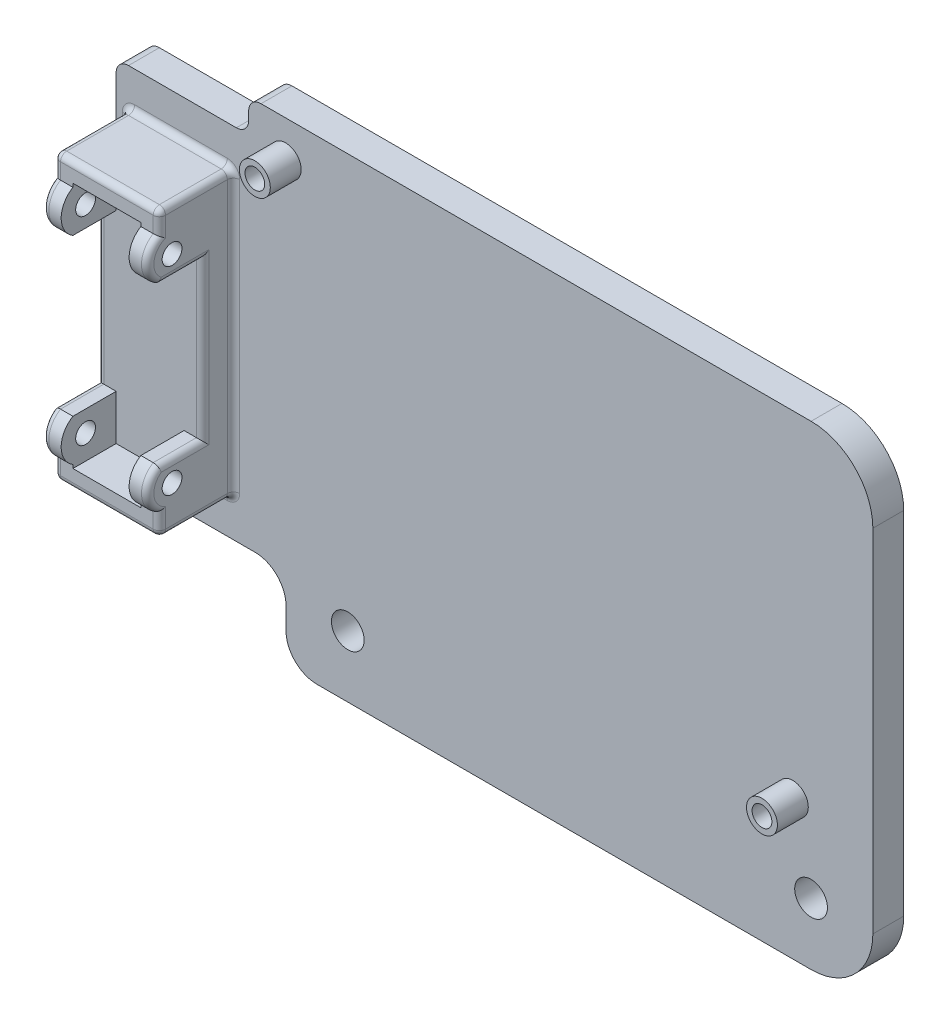
SolidWorks part; units mm, degrees
ref_plane "Front Plane" through (0, 0, 0) normal (0, 0, 1) x (1, 0, 0)
ref_plane "Top Plane" through (0, 0, 0) normal (0, 1, 0) x (1, 0, 0)
ref_plane "Right Plane" through (0, 0, 0) normal (1, 0, 0) x (0, 0, -1)
sketch "Sketch1" plane through (0, 0, 0) normal (0, 0, 1) x (1, 0, 0)
  line L17 (20, 20) -> (130, 20)
  line L18 (20, 20) -> (20, 80)
  line L19 (20, 80) -> (130, 80)
  line L20 (130, 20) -> (130, 80)
  line L21 (0, 0) -> (150, 0)
  line L22 (0, 0) -> (0, 85)
  line L23 (0, 85) -> (150, 85)
  line L24 (150, 0) -> (150, 85)
  circle A0 centre (37.5, 10) radius 2.65
  circle A1 centre (112.5, 10) radius 2.65
  dimension "D5" = 5.3
  dimension "D8" = 5.3
  dimension "D1" = 20
  dimension "D2" = 20
  dimension "D3" = 5
  dimension "D4" = 20
  dimension "D6" = 110
  dimension "D7" = 60
  dimension "D9" = 75
  dimension "D10" = 37.5
  dimension "D11" = 37.5
  dimension "D12" = 10
extrude "Boss-Extrude1" add sketch "Sketch1" along normal blind 5 contours L22 L21 L24 L23 | A0 | A1
sketch "Sketch2" plane through (0, 0, 5) normal (0, 0, 1) x (1, 0, 0)
  line L0 (27.4544, 70.8762) -> (24.25, 70.8762)
  line L1 (24.25, 80.4) -> (125.75, 80.4)
  line L2 (24.25, 80.4) -> (24.25, 20)
  line L3 (24.25, 20) -> (125.75, 20)
  line L4 (125.75, 80.4) -> (125.75, 20)
  line L5 (24.25, 70.8762) -> (27.4544, 70.8762)
  line L6 (27.4544, 70.8762) -> (27.4544, 80.4)
  line L7 (109.5494, 22.54) -> (109.5494, 20)
  line L8 (109.5494, 22.54) -> (125.75, 22.54)
  line L9 (20, 20) -> (130, 20) construction
  line L10 (20, 80) -> (130, 80) construction
  line L11 (150, 0) -> (150, 85) construction
  circle A0 centre (27.4544, 70.8762) radius 1.6
  circle A1 centre (109.5494, 22.54) radius 1.6
  point P18 (75, 80.4)
  dimension "D14" = 3.2
  dimension "D15" = 3.2
  dimension "D1" = 9.5238
  dimension "D2" = 3.2044
  dimension "D3" = 60.4
  dimension "D4" = 101.5
  dimension "D5" = 16.2006
  dimension "D6" = 2.54
  dimension "D7" = 0
  dimension "D8" = 0.4
  dimension "D9" = 75
  dimension "D10" = 9.5238
  dimension "D11" = 3.2044
  dimension "D12" = 16.2006
  dimension "D13" = 2.54
extrude "Cut-Extrude1" cut sketch "Sketch2" against normal blind 5 contours L0 A0 L6 | L6 A0 L0 | L7 A1 L8 | L8 A1 L7 region at (27.6808, 70.6498, 5) region at (26.7753, 71.5553, 5) region at (109.3231, 22.7664, 5) region at (110.2285, 21.8609, 5)
sketch "Sketch3" plane through (0, 0, 5) normal (0, 0, 1) x (1, 0, 0)
  circle A0 centre (27.4544, 70.8762) radius 2.5
  circle A1 centre (27.4544, 70.8762) radius 1.6
  circle A2 centre (109.5494, 22.54) radius 1.6
  circle A3 centre (109.5494, 22.54) radius 2.5
  dimension "D1" = 3.2
  dimension "D2" = 5
  dimension "D3" = 3.2
  dimension "D4" = 5
extrude "Boss-Extrude2" add sketch "Sketch3" along normal blind 5
ref_plane "Plane1" through (0, 0, 11) normal (0, 0, 1) x (1, 0, 0)
sketch "Sketch4" plane through (0, 0, 0) normal (0, 0, -1) x (-1, 0, 0)
  circle A0 centre (-27.4544, 70.8762) radius 3
  circle A1 centre (-27.4544, 70.8762) radius 1.6
  circle A2 centre (-109.5494, 22.54) radius 3
  circle A3 centre (-109.5494, 22.54) radius 1.6
  dimension "D1" = 3.2
  dimension "D2" = 3.2
  dimension "D3" = 6
  dimension "D4" = 6
extrude "Cut-Extrude2" cut sketch "Sketch4" against normal blind 3.2
sketch "Sketch5" plane through (0, 0, 11) normal (0, 0, 1) x (1, 0, 0)
  line L1 (16, 22.5) -> (5, 22.5)
  line L2 (16, 22.5) -> (16, 62.5)
  line L3 (16, 62.5) -> (5, 62.5)
  line L4 (5, 22.5) -> (5, 62.5)
  line L5 (0, 0) -> (150, 0) construction
  line L6 (0, 0) -> (0, 85) construction
  line L8 (19, 19.5) -> (2, 19.5)
  line L9 (19, 19.5) -> (19, 65.5)
  line L10 (19, 65.5) -> (2, 65.5)
  line L11 (2, 19.5) -> (2, 65.5)
  point P6 (5, 42.5)
  dimension "D1" = 40
  dimension "D2" = 42.5
  dimension "D3" = 11
  dimension "D4" = 5
  dimension "D5" = 3
  dimension "D6" = 3
  dimension "D7" = 3
  dimension "D8" = 3
extrude "Boss-Extrude3" add sketch "Sketch5" along normal blind 6 and the other way up to next
sketch "Sketch6" plane through (2, 0, 0) normal (-1, 0, 0) x (0, 0, 1)
  line L0 (47.05, 26.45) -> (14.95, 26.45)
  line L1 (47.05, 26.45) -> (47.05, 58.55)
  line L2 (47.05, 58.55) -> (14.95, 58.55)
  line L3 (14.95, 26.45) -> (14.95, 58.55)
  line L4 (51, 22.5) -> (11, 22.5)
  line L5 (51, 22.5) -> (51, 62.5)
  line L6 (51, 62.5) -> (11, 62.5)
  line L7 (11, 22.5) -> (11, 62.5)
  line L8 (51, 22.5) -> (47.05, 26.45)
  line L9 (11, 22.5) -> (14.95, 26.45)
  line L10 (47.05, 58.55) -> (51, 62.5)
  line L11 (14.95, 58.55) -> (11, 62.5)
  line L13 (17, 65.5) -> (5, 65.5) construction
  line L14 (11, -46.75) -> (11, 46.75) construction
  circle A0 centre (14.95, 58.55) radius 1.6
  circle A1 centre (14.95, 26.45) radius 1.6
  dimension "D8" = 3.2
  dimension "D9" = 3.2
  dimension "D1" = 40
  dimension "D2" = 40
  dimension "D3" = 32.1
  dimension "D4" = 3.95
  dimension "D5" = 3.95
  dimension "D6" = 0
  dimension "D7" = 3
extrude "Cut-Extrude3" cut sketch "Sketch6" against normal blind 33 contours L11 A0 L3 | L3 A0 L2 | L2 A0 L11 | L9 A1 L0 | L0 A1 L3 | L3 A1 L9 region at (2, 25.6772, 15.2701) region at (2, 27.1291, 15.6291) region at (2, 26.7701, 14.1772) region at (2, 57.8709, 15.6291) region at (2, 59.3228, 15.2701) region at (2, 58.2299, 14.1772)
sketch "Sketch7" plane through (2, 0, 0) normal (-1, 0, 0) x (0, 0, 1)
  line L0 (17, 55.1736) -> (17, 61.9264)
  line L1 (17, 65.5) -> (17, 19.5) construction
  line L2 (17, 29.8264) -> (17, 23.0736)
  circle A0 centre (14.95, 58.55) radius 3.95
  circle A1 centre (14.95, 26.45) radius 3.95
  line M7 (17, 19.5) -> (17, 65.5)
  dimension "D1" = 7.9
  dimension "D2" = 7.9
extrude "Boss-Extrude4" add sketch "Sketch7" against normal up to surface (17 mm away) contours A0 M7 | A1 M7 region at (2, 58.55, 17.7782) region at (2, 26.45, 17.7782) up to face at (19, 58.55, 13.35)
sketch "Sketch8" plane through (0, 0, 17) normal (0, 0, 1) x (1, 0, 0)
  line L1 (16, 22.5) -> (5, 22.5)
  line L2 (16, 22.5) -> (16, 62.5)
  line L3 (16, 62.5) -> (5, 62.5)
  line L4 (5, 22.5) -> (5, 62.5)
extrude "Cut-Extrude4" cut sketch "Sketch8" along normal blind 33
sketch "Sketch9" plane through (2, 0, 0) normal (-1, 0, 0) x (0, 0, 1)
  line L0 (5, 65.5) -> (5, 19.5) construction
  line L1 (17, 55.1736) -> (5, 55.1736)
  line L2 (17, 55.1736) -> (17, 29.8264)
  line L3 (17, 29.8264) -> (5, 29.8264)
  line L4 (5, 55.1736) -> (5, 29.8264)
  dimension "D1" = 0
extrude "Cut-Extrude5" cut sketch "Sketch9" against normal blind 33
sketch "Sketch10" plane through (0, 0, 5) normal (0, 0, 1) x (1, 0, 0)
  line L1 (16, 62.5) -> (5, 62.5)
  line L2 (16, 62.5) -> (16, 22.5)
  line L3 (16, 22.5) -> (5, 22.5)
  line L4 (5, 62.5) -> (5, 22.5)
  line L5 (19, 29.8264) -> (16, 29.8264)
  line L6 (19, 29.8264) -> (19, 55.1736)
  line L7 (19, 55.1736) -> (16, 55.1736)
  line L8 (16, 29.8264) -> (16, 55.1736)
  line L9 (2, 29.8264) -> (5, 29.8264)
  line L10 (2, 29.8264) -> (2, 55.1736)
  line L11 (2, 55.1736) -> (5, 55.1736)
  line L12 (5, 29.8264) -> (5, 55.1736)
  line M2 (19, 55.1736) -> (16, 55.1736)
  line M3 (16, 55.1736) -> (16, 62.5)
  line M4 (16, 62.5) -> (5, 62.5)
  line M5 (5, 62.5) -> (5, 55.1736)
  line M6 (5, 55.1736) -> (2, 55.1736)
  line M9 (16, 29.8264) -> (19, 29.8264)
  line M13 (2, 29.8264) -> (5, 29.8264)
  line M14 (5, 29.8264) -> (5, 22.5)
  line M15 (5, 22.5) -> (16, 22.5)
  line M16 (16, 22.5) -> (16, 29.8264)
extrude "Boss-Extrude5" add sketch "Sketch10" along normal blind 5 contours L6 L2 M9 M2 | L4 L2 M5 M14 M15 M16 M3 M4 | L10 L4 M13 M6 region at (10.5, 42.5, 5) region at (17.5, 42.5, 5) region at (3.5, 42.5, 5)
fillet "Fillet1" radius 1 24 edges at (19, 58.55, 18.9) (19, 63.7132, 17) (19, 42.5, 5) (19, 21.2868, 17) (19, 26.45, 18.9) (19, 29.8264, 13.5) (19, 42.5, 10) (19, 55.1736, 13.5) (2, 42.5, 10) (2, 29.8264, 13.5) (2, 26.45, 18.9) (2, 21.2868, 17) (2, 42.5, 5) (2, 63.7132, 17) (2, 58.55, 18.9) (2, 55.1736, 13.5) (19, 65.5, 11) (10.5, 65.5, 17) (2, 65.5, 11) (10.5, 65.5, 5) (2, 19.5, 11) (10.5, 19.5, 17) (19, 19.5, 11) (10.5, 19.5, 5)
sketch "Sketch11" plane through (0, 0, 5) normal (0, 0, 1) x (1, 0, 0)
  line L0 (0, 0) -> (150, 0) construction
  line L1 (122.5, 0) -> (150, 0)
  line L2 (122.5, 10) -> (122.5, 66.8762)
  line L3 (122.5, 85) -> (150, 85)
  line L4 (150, 0) -> (150, 85)
  line L5 (150, 0) -> (150, 85) construction
  line L6 (0, 85) -> (150, 85) construction
  line L7 (112.5, 0) -> (32.5, 0)
  line L8 (112.5, 76.8762) -> (23.4544, 76.8762)
  line L9 (0, 0) -> (0, 85) construction
  line L10 (18, 18.5) -> (3, 18.5) construction
  line L11 (27.5, 0) -> (0, 0)
  line L12 (27.5, 5) -> (27.5, 8.5)
  line L13 (22.5, 13.5) -> (2, 13.5)
  line L14 (0, 0) -> (0, 13.5)
  line L15 (27.5, 0) -> (112.5, 0)
  line L16 (3, 66.5) -> (18, 66.5) construction
  line L18 (21.4544, 74.8762) -> (21.4544, 73.5)
  line L19 (19.4544, 71.5) -> (2, 71.5)
  line L20 (0, 76.8762) -> (0, 71.5)
  line L21 (0, 15.5) -> (0, 69.5)
  circle A0 centre (112.5, 10) radius 2.65 construction
  arc A1 (122.5, 10) -> (112.5, 0) centre (112.5, 10) cw
  circle A2 centre (27.4544, 70.8762) radius 1.6 construction
  arc A3 (112.5, 76.8762) -> (122.5, 66.8762) centre (112.5, 66.8762) cw
  circle A4 centre (37.5, 10) radius 2.65 construction
  arc A5 (27.5, 8.5) -> (22.5, 13.5) centre (22.5, 8.5) ccw
  arc A6 (27.5, 5) -> (32.5, 0) centre (32.5, 5) ccw
  circle A7 centre (27.4544, 70.8762) radius 2.5 construction
  arc A8 (23.4544, 76.8762) -> (21.4544, 74.8762) centre (23.4544, 74.8762) ccw
  arc A9 (21.4544, 73.5) -> (19.4544, 71.5) centre (19.4544, 73.5) cw
  arc A10 (2, 13.5) -> (0, 15.5) centre (2, 15.5) cw
  arc A11 (2, 71.5) -> (0, 69.5) centre (2, 69.5) ccw
  line M26 (150, 85) -> (0, 85)
  line M27 (0, 85) -> (0, 0)
  line M28 (0, 0) -> (150, 0)
  line M29 (150, 0) -> (150, 85)
  dimension "D2" = 10
  dimension "D4" = 10
  dimension "D7" = 5
  dimension "D8" = 5
  dimension "D11" = 2
  dimension "D12" = 2
  dimension "D13" = 2
  dimension "D1" = 10
  dimension "D3" = 6
  dimension "D5" = 10
  dimension "D6" = 5
  dimension "D9" = 6
  dimension "D10" = 5
extrude "Cut-Extrude6" cut sketch "Sketch11" against normal blind 10 contours A11 L19 A9 L18 A8 L8 A3 L2 A1 M28 M29 M26 M27 | L13 A10 A6 L12 A5 M27 M28 region at (117.5, 0.1724, 5) region at (13.7515, 6.6042, 5)
